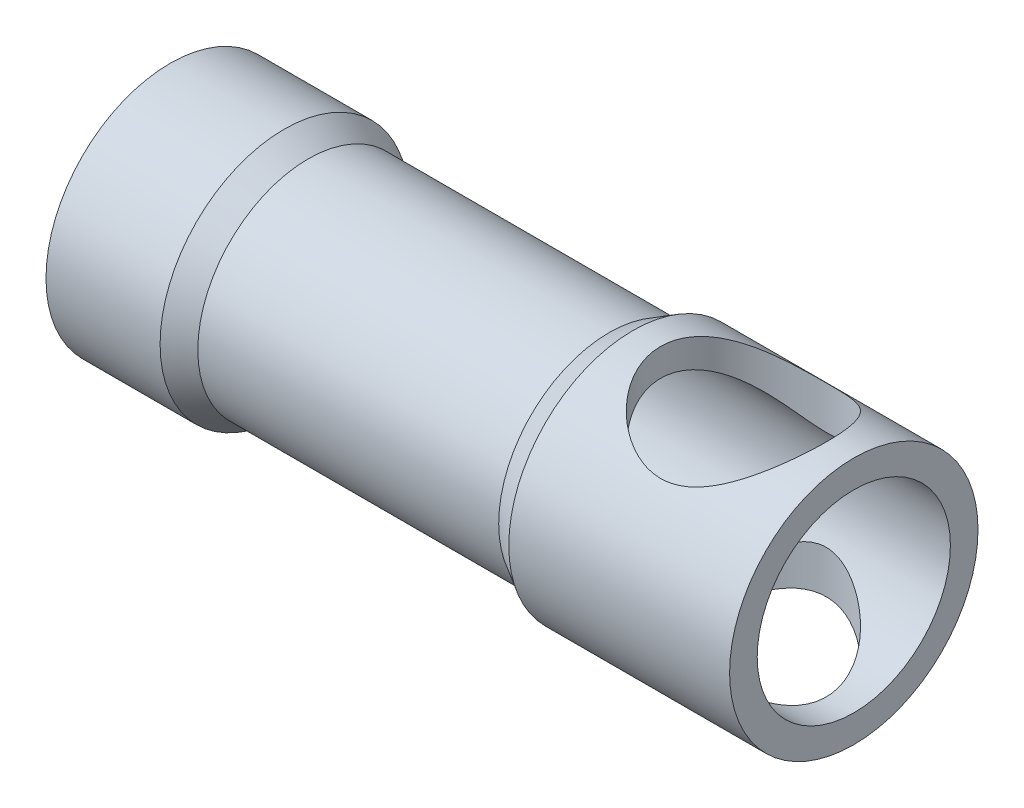
SolidWorks part; units mm, degrees
ref_plane "Front Plane" through (0, 0, 0) normal (0, 0, 1) x (1, 0, 0)
ref_plane "Top Plane" through (0, 0, 0) normal (0, 1, 0) x (1, 0, 0)
ref_plane "Right Plane" through (0, 0, 0) normal (1, 0, 0) x (0, 0, -1)
sketch "Sketch1" plane through (0, 0, 0) normal (0, 0, 1) x (1, 0, 0)
  line L0 (0, 0) -> (43.7471, 0) construction
  line L1 (0, 6) -> (0, 14.2875)
  line L2 (0, 14.2875) -> (13.1254, 14.2875)
  line L3 (78.6384, 14.2875) -> (78.6384, 11.1125)
  line L4 (78.6384, 11.1125) -> (15.875, 11.1125)
  line L5 (13.1254, 14.2875) -> (15.875, 12.7)
  line L8 (15.875, 11.1125) -> (15.875, 6)
  line L9 (15.875, 6) -> (0, 6)
  line L10 (15.875, 12.7) -> (50.4888, 12.7)
  line L11 (50.4888, 12.7) -> (53.2384, 14.2875)
  line L12 (15.875, 11.1125) -> (15.875, 12.7) construction
  line L13 (53.2384, 14.2875) -> (78.6384, 14.2875)
  dimension "D1" = 6
  dimension "D2" = 14.2875
  dimension "D3" = 15.875
  dimension "D4" = 78.6384
  dimension "D5" = 25.4
  dimension "D6" = 30
  dimension "D7" = 30
  dimension "D8" = 1.5875
  dimension "D9" = 3.175
revolve "Revolve1" add sketch "Sketch1" angle 360 about L0
thread "Thread1" pitch 1.5 method cut profile "Thread Profile1" start angle 0, offset 0, length 19.05, pitch 1.5, diameter 12
ref_plane "Plane1" through (0, 0, -6) normal (0, -1, 0) x (0, 0, -1)
sketch "Thread Profile1" plane through (0, 0, -6) normal (0, -1, 0) x (0, 0, -1)
  line L0 (0, 0) -> (0, 1.5) construction
  line L1 (0, 0) -> (0.8119, 0.4687)
  line L2 (0.8119, 0.4687) -> (0.8119, 0.6562)
  line L3 (0.8119, 0.6562) -> (0, 1.125)
  line L4 (0.8119, 0.5625) -> (0, 0.5625) construction
  line L11 (0, 0) -> (0, 1.125)
  point P2 (0, 0)
  dimension "Pitch" = 1.5
  dimension "Profile_Angle" = 60
  dimension "Profile_Land" = 0.1875
  dimension "Profile_Height" = 0.8119
sketch "Sketch4" plane through (0, 0, 0) normal (0, 1, 0) x (1, 0, 0)
  line L0 (0, 0) -> (78.6384, 0) construction
  line L1 (0, 14.2875) -> (0, -14.2875) construction
  line L2 (78.6384, -14.2875) -> (78.6384, 14.2875) construction
  line L3 (65.9384, 0) -> (78.6384, 0) construction
  circle A0 centre (65.9384, 0) radius 9.525
  dimension "D1" = 19.05
  dimension "D2" = 12.7
extrude "Cut-Extrude1" cut sketch "Sketch4" against normal mid plane 50.8
